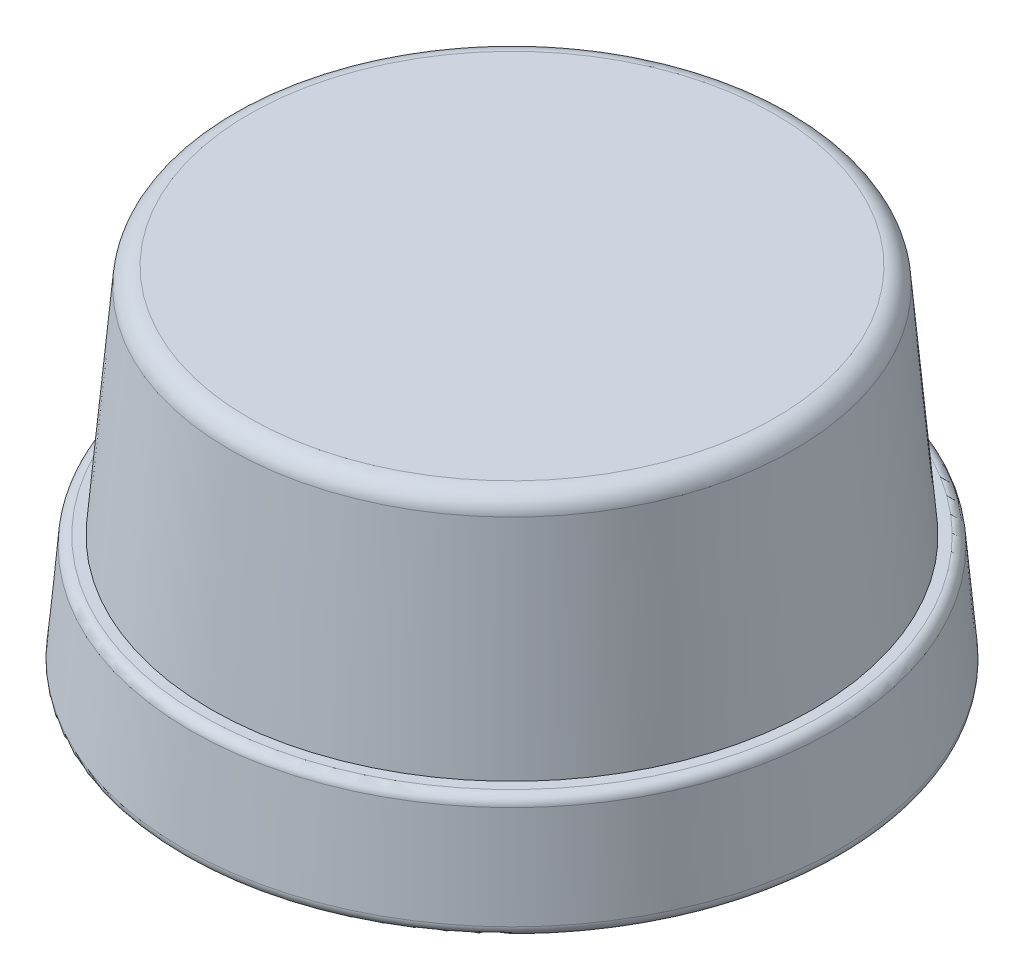
SolidWorks part; units mm, degrees
ref_plane "Front" through (0, 0, 0) normal (0, 0, 1) x (1, 0, 0)
ref_plane "Top" through (0, 0, 0) normal (0, 1, 0) x (1, 0, 0)
ref_plane "Right" through (0, 0, 0) normal (1, 0, 0) x (0, 0, -1)
sketch "Sketch1" plane through (0, 0, 0) normal (0, 1, 0) x (1, 0, 0)
  circle A0 centre (0, 0) radius 17
  dimension "D1" = 34
extrude "Boss-Extrude1" add sketch "Sketch1" along normal blind 6 draft 5
sketch "Sketch2" plane through (0, 6, 0) normal (0, 1, 0) x (1, 0, 0)
  circle A0 centre (0, 0) radius 15.5
  dimension "D1" = 31
extrude "Boss-Extrude2" add sketch "Sketch2" along normal blind 12 draft 5
sketch "Sketch3" plane through (0, 0, 0) normal (0, -1, 0) x (1, 0, 0)
  circle A1 centre (0, 0) radius 3.05
  dimension "D1" = 6.1
extrude "Cut-Extrude1" cut sketch "Sketch3" against normal blind 17
sketch "Sketch4" plane through (0, 0, 0) normal (0, -1, 0) x (1, 0, 0)
  line L1 (-2.4384, -7.2384) -> (2.4384, -7.2384)
  line L2 (-2.4384, -7.2384) -> (-2.4384, -3.6824)
  line L3 (-2.4384, -3.6824) -> (2.4384, -3.6824)
  line L4 (2.4384, -7.2384) -> (2.4384, -3.6824)
  point P4 (0, -3.6824)
  point P6 (2.4384, -5.4604)
  dimension "D1" = 1.778
  dimension "D2" = 4.8768
extrude "Cut-Extrude2" [suppressed] cut sketch "Sketch4" against normal blind 6.35
sketch "Sketch5" [suppressed] plane through (0, 0, -3.6824) normal (0, 0, -1) x (-1, 0, 0)
  line L5 (0, 0) -> (0, 6.35) construction
  line L6 (-2.4384, 0) -> (2.4384, 0) construction
  line L7 (-2.4384, 6.35) -> (2.4384, 6.35) construction
  circle A1 centre (0, 3.175) radius 1.2065
  dimension "D1" = 2.413
extrude "Cut-Extrude3" [suppressed] cut sketch "Sketch5" against normal blind 4 contours A1
sketch "Sketch6" [suppressed] plane through (0, 0, -7.2384) normal (0, 0, 1) x (1, 0, 0)
  line L0 (0, -0.0882) -> (0, 6.4715) construction
  circle A0 centre (0, 3.1917) radius 1.143
  dimension "D1" = 2.286
extrude "Cut-Extrude4" [suppressed] cut sketch "Sketch6" against normal blind 4
sketch "Sketch7" [suppressed] plane through (0, 0, -7.2384) normal (0, 0, 1) x (1, 0, 0)
  circle A0 centre (0, 3.1917) radius 2.159
  dimension "D1" = 4.318
extrude "Cut-Extrude5" [suppressed] cut sketch "Sketch7" against normal blind 4 from offset 1.5 offset against normal yes
fillet "Fillet1" radius 1 1 edges at (0, 18, 14.4501)
fillet "Fillet2" radius 0.5 1 edges at (0, 6, 16.4751)
sketch "Sketch8" plane through (0, 0, 0) normal (0, -1, 0) x (1, 0, 0)
  circle A0 centre (0, 0) radius 4.5
  dimension "D1" = 9
extrude "Cut-Extrude6" cut sketch "Sketch8" against normal blind 8
fillet "Fillet3" radius 0.5 1 edges at (0, 0, 17)
